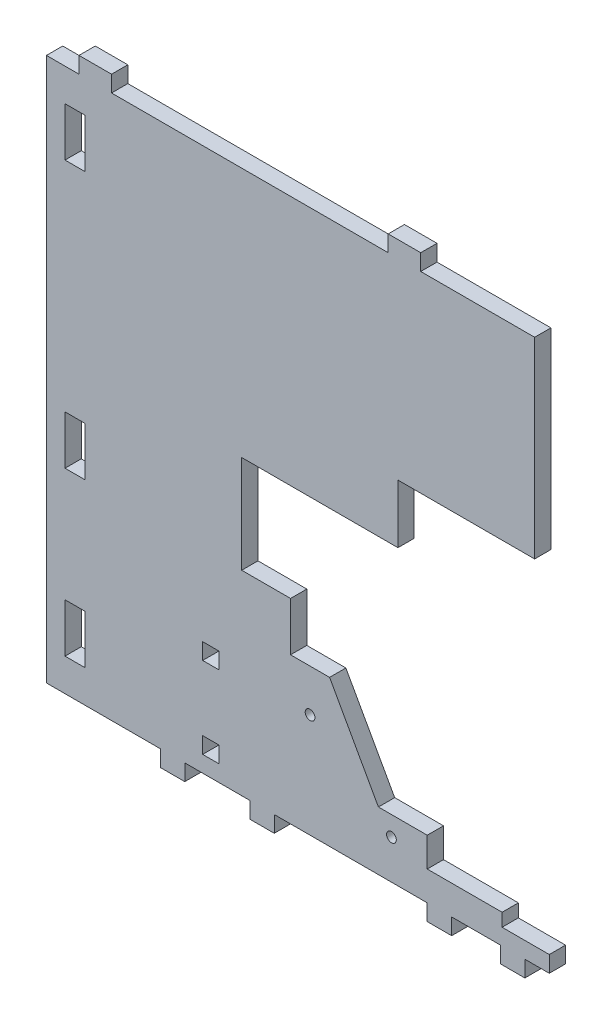
SolidWorks part; units mm, degrees
ref_plane "Plan de face" through (0, 0, 0) normal (0, 0, 1) x (1, 0, 0)
ref_plane "Plan de dessus" through (0, 0, 0) normal (0, 1, 0) x (1, 0, 0)
ref_plane "Plan de droite" through (0, 0, 0) normal (1, 0, 0) x (0, 0, -1)
sketch "Esquisse1" plane through (0, 0, 0) normal (0, 0, 1) x (1, 0, 0)
  line L1 (0, 0) -> (37, 0)
  line L2 (0, 0) -> (0, 45)
  line L3 (0, 45) -> (12, 45)
  line L4 (37, 0) -> (37, 18)
  line L6 (12, 45) -> (27, 18)
  line L7 (27, 18) -> (37, 18)
  circle A0 centre (6, 32) radius 1.5
  circle A1 centre (31, 12) radius 1.5
  dimension "D3" = 20
  dimension "D4" = 3
  dimension "D1" = 6
  dimension "D2" = 45
  dimension "D5" = 12
  dimension "D6" = 12
  dimension "D7" = 25
  dimension "D8" = 6
  dimension "D9" = 6
  dimension "D10" = 10
extrude "Boss.-Extru.1" add sketch "Esquisse1" along normal blind 5
sketch "Esquisse2" plane through (0, 0, 5) normal (0, 0, 1) x (1, 0, 0)
  line L0 (37, 18) -> (27, 18) construction
  line L1 (37, 0) -> (42, 0)
  line L2 (37, 0) -> (37, 18)
  line L3 (49.5, 0) -> (64.5, 0)
  line L4 (12, 45) -> (0, 45) construction
  line L5 (72, 0) -> (72, -5)
  line L6 (72, -5) -> (64.5, -5)
  line L7 (64.5, 0) -> (64.5, -5)
  line L8 (72, 0) -> (79.5, 0)
  line L9 (49.5, 0) -> (49.5, -5)
  line L10 (49.5, -5) -> (42, -5)
  line L11 (42, 0) -> (42, -5)
  line L12 (0, 0) -> (-5, 0)
  line L13 (0, 0) -> (0, 60)
  line L14 (0, 60) -> (-15, 60)
  line L15 (40, 167) -> (75, 167)
  line L16 (-12.5, 0) -> (-32.5, 0)
  line L17 (-40, 0) -> (-40, -5)
  line L18 (-15, 60) -> (-15, 90)
  line L19 (-40, -5) -> (-32.5, -5)
  line L20 (-75, 0) -> (-75, 167)
  line L21 (-75, 167) -> (-65, 167)
  line L22 (-32.5, 0) -> (-32.5, -5)
  line L23 (33, 90) -> (-15, 90)
  line L24 (75, 167) -> (75, 108)
  line L25 (-12.5, 0) -> (-12.5, -5)
  line L26 (-12.5, -5) -> (-5, -5)
  line L27 (-5, 0) -> (-5, -5)
  line L28 (-40, 0) -> (-75, 0)
  line L29 (-65, 167) -> (-65, 172)
  line L30 (-65, 172) -> (-55, 172)
  line L31 (-55, 167) -> (-55, 172)
  line L32 (-55, 167) -> (30, 167)
  line L33 (40, 167) -> (40, 172)
  line L34 (40, 172) -> (30, 172)
  line L35 (30, 167) -> (30, 172)
  line L36 (-69.2981, 10) -> (-63.1592, 10)
  line L37 (-69.2981, 10) -> (-69.2981, 25)
  line L38 (33, 90) -> (33, 108)
  line L39 (33, 108) -> (75, 108)
  line L40 (-63.1592, 10) -> (-63.1592, 25)
  line L41 (-69.2981, 25) -> (-63.1592, 25)
  line L42 (-69.2981, 10) -> (-69.2981, 0) construction
  line L43 (-63.1592, 25) -> (-63.1592, 10) construction
  line L45 (-69.2981, 75) -> (-63.1592, 75)
  line L46 (-69.2981, 75) -> (-69.2981, 60)
  line L47 (-69.2981, 60) -> (-63.1592, 60)
  line L48 (-63.1592, 75) -> (-63.1592, 60)
  line L49 (-69.2981, 142) -> (-63.1592, 142)
  line L50 (-69.2981, 142) -> (-69.2981, 157)
  line L51 (-69.2981, 157) -> (-63.1592, 157)
  line L52 (-63.1592, 142) -> (-63.1592, 157)
  line L53 (-22, 5) -> (-27, 5)
  line L54 (-22, 5) -> (-22, 10)
  line L55 (-22, 10) -> (-27, 10)
  line L56 (-27, 5) -> (-27, 10)
  line L57 (-27, 35) -> (-22, 35)
  line L58 (-27, 35) -> (-27, 30)
  line L59 (-27, 30) -> (-22, 30)
  line L60 (-22, 35) -> (-22, 30)
  line L62 (37, 18) -> (42, 18)
  line L63 (37, 18) -> (37, 8.9214)
  line L64 (65, 9) -> (65, 5)
  line L65 (42, 18) -> (42, 9)
  line L66 (65, 5) -> (79.5, 5)
  line L67 (79.5, 0) -> (79.5, 5)
  line L68 (65, 9) -> (42, 9)
  circle A0 centre (31, 12) radius 1.5 construction
  line M2 (0, 45) -> (0, 0)
  line M4 (37, 0) -> (37, 18)
  dimension "D24" = 11
  dimension "D25" = 3
  dimension "D1" = 42.5
  dimension "D2" = 7.5
  dimension "D3" = 5
  dimension "D4" = 5
  dimension "D5" = 15
  dimension "D6" = 15
  dimension "D7" = 15
  dimension "D8" = 167
  dimension "D9" = 18
  dimension "D10" = 5
  dimension "D11" = 20
  dimension "D12" = 75
  dimension "D13" = 75
  dimension "D14" = 5
  dimension "D15" = 10
  dimension "D16" = 85
  dimension "D17" = 10
  dimension "D18" = 48
  dimension "D19" = 10
  dimension "D20" = 15
  dimension "D21" = 35
  dimension "D22" = 10
  dimension "D23" = 30
  dimension "D26" = 5
  dimension "D27" = 23
extrude "Boss.-Extru.2" add sketch "Esquisse2" against normal blind 5 contours L64 L68 L65 L62 L2 L1 L11 L10 L9 L3 L7 L6 L5 L8 L67 L66 M4 | L38 L39 L24 L15 L33 L34 L35 L32 L31 L30 L29 L21 L20 L28 L17 L19 L22 L16 L25 L26 L27 L12 L13 L14 L18 L23 L53 L56 L55 L54 L52 L49 L50 L51 L37 L41 L40 L36 L45 L48 L47 L46 L57 L60 L59 M2 region at (54.3141, 3.9038, 5) region at (-16.1716, 98.7738, 5)
